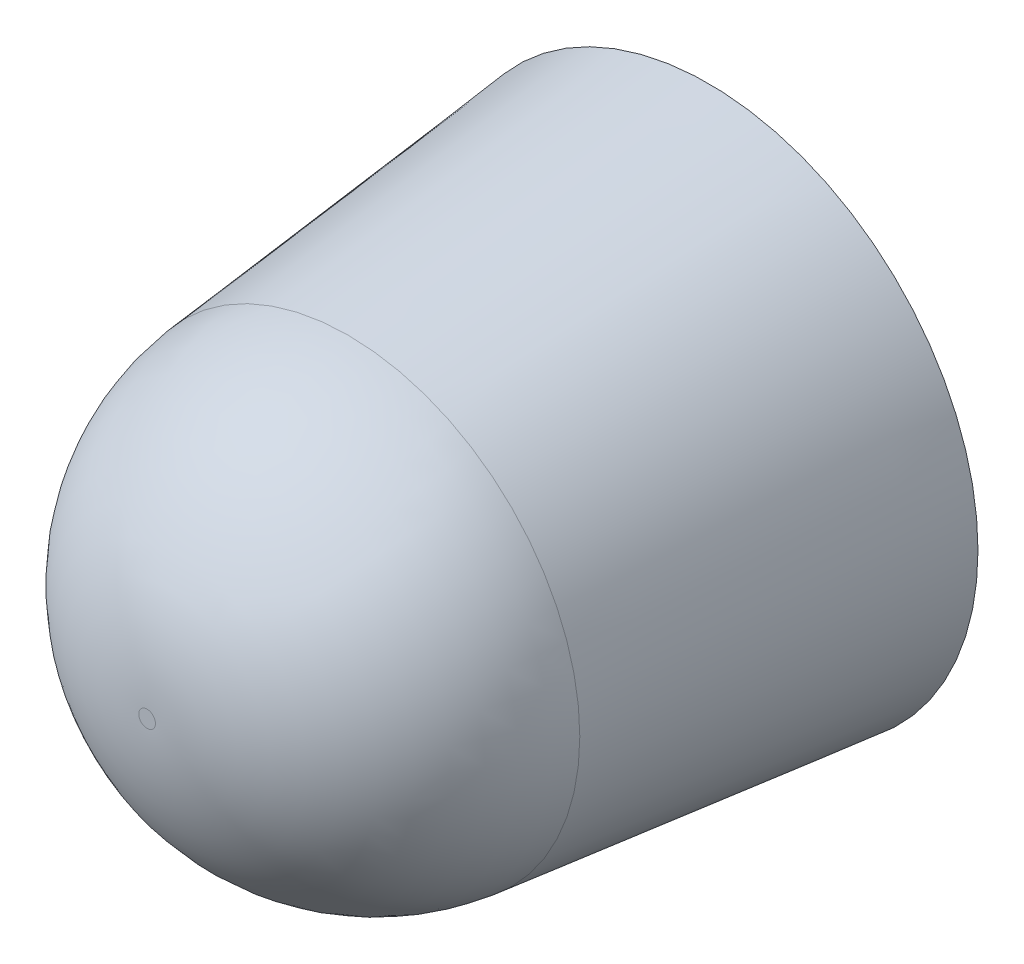
SolidWorks part; units mm, degrees
material "PVC 0.007 Plasticized"
ref_plane "Front Plane" through (0, 0, 0) normal (0, 0, 1) x (1, 0, 0)
ref_plane "Top Plane" through (0, 0, 0) normal (0, 1, 0) x (1, 0, 0)
ref_plane "Right Plane" through (0, 0, 0) normal (1, 0, 0) x (0, 0, -1)
sketch "Sketch1" plane through (0, 0, 0) normal (0, 0, 1) x (1, 0, 0)
  circle A0 centre (0, 0) radius 75
  dimension "D1" = 150
extrude "Boss-Extrude1" add sketch "Sketch1" along normal blind 200
draft "Draft1" type of draft neutral plane draft angle 6 faces to draft 1 face at (75, 0, 200) neutral plane through (0, 0, 200) neutral plane normal (0, 0, 1) parameters "D1"=6
fillet "Fillet1" radius 80 1 edges at (75, 0, 200)
shell "Shell1" thickness 10 removed face at (96.0208, 0, 0)
fillet "Fillet2" radius 60 1 edges at (85.9658, 0, 0)
